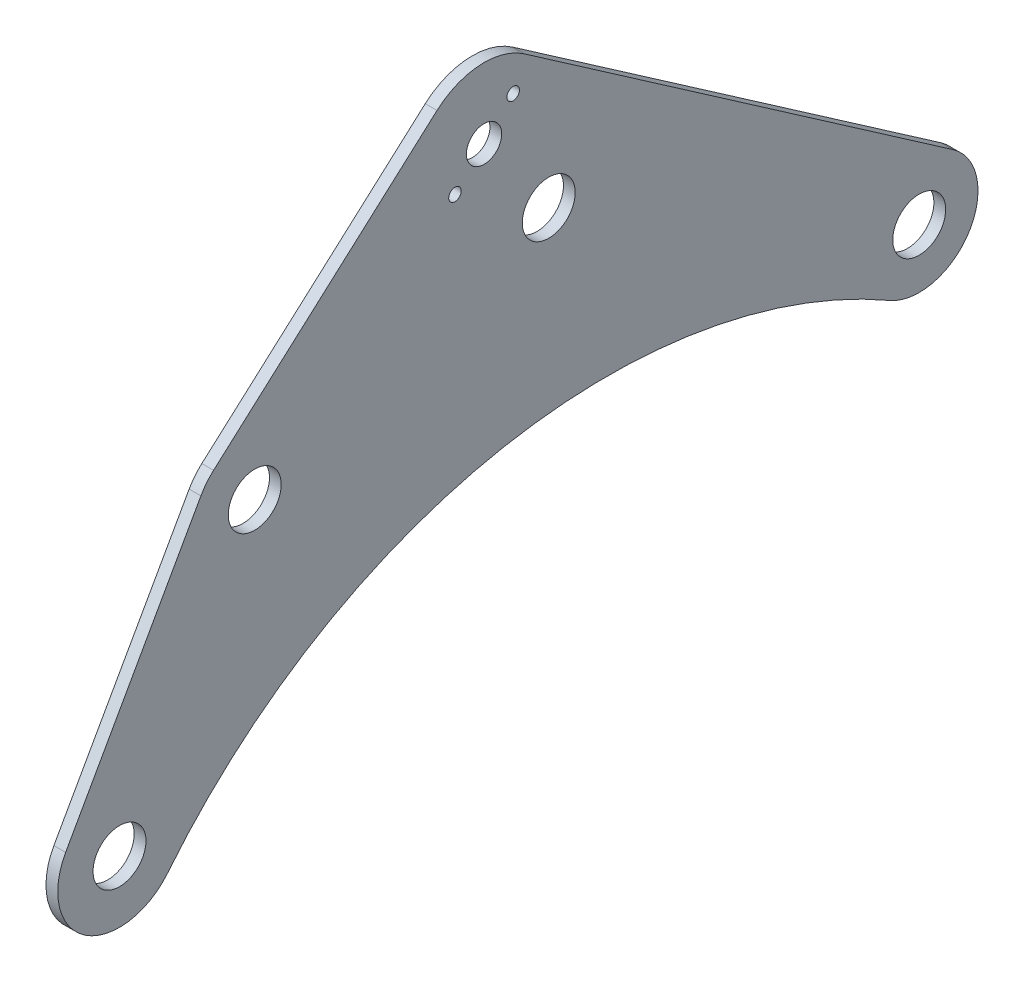
SolidWorks part; units mm, degrees
material "Acrylic (Medium-high impact)"
ref_plane "Front Plane" through (0, 0, 0) normal (0, 0, 1) x (1, 0, 0)
ref_plane "Top Plane" through (0, 0, 0) normal (0, 1, 0) x (1, 0, 0)
ref_plane "Right Plane" through (0, 0, 0) normal (1, 0, 0) x (0, 0, -1)
sketch "Sketch1" plane through (0, 0, 0) normal (1, 0, 0) x (0, 0, -1)
  line L0 (-548.7618, -304.8) -> (152.435, -304.8)
  line L1 (-192.8252, -120.65) -> (-152.4, -120.65)
  line L2 (-234.95, -162.7748) -> (-234.95, -205.5252)
  line L3 (-192.8252, -247.65) -> (-152.4, -247.65)
  line L4 (-152.4, -120.65) -> (-152.4, -247.65)
  circle A1 centre (0, 0) radius 6.35
  circle A6 centre (-431.8, -79.375) radius 12.7
  circle A7 centre (-358.775, 50.8) radius 12.7
  circle A8 centre (-200.025, 107.95) radius 12.7
  arc A9 (-234.95, -205.5252) -> (-192.8252, -247.65) centre (-192.8252, -205.5252) ccw
  arc A10 (-192.8252, -120.65) -> (-234.95, -162.7748) centre (-192.8252, -162.7748) ccw
  circle A11 centre (-358.775, -182.354) radius 120.65
  circle A12 centre (-234.95, 155.194) radius 29.845
  dimension "D1" = 12.7
  dimension "D2" = 25.4
  dimension "D3" = 42.1248
  dimension "D4" = 127
  dimension "D7" = 184.15
  dimension "D6" = 241.3
  dimension "D16" = 59.69
  dimension "D5" = 82.55
  dimension "D8" = 304.8
  dimension "D9" = 152.4
  dimension "D10" = 431.8
  dimension "D11" = 79.375
  dimension "D12" = 358.775
  dimension "D13" = 50.8
  dimension "D14" = 200.025
  dimension "D15" = 107.95
  dimension "D17" = 234.95
  dimension "D18" = 155.194
sketch "Sketch2" plane through (0, 0, 0) normal (1, 0, 0) x (0, 0, -1)
  line L1 (-460.8751, -63.0646) -> (-387.8501, 67.1104)
  line L3 (-381.0036, 75.6451) -> (-260.3541, 183.5884)
  line L5 (-213.2394, 186.5031) -> (18.0922, 26.0909)
  arc A0 (-381.0036, 75.6451) -> (-387.8501, 67.1104) centre (-358.775, 50.8) ccw
  arc A2 (-460.8751, -63.0646) -> (-405.83, -100.2783) centre (-431.8, -79.375) ccw
  arc A4 (-213.2394, 186.5031) -> (-260.3541, 183.5884) centre (-234.95, 155.194) ccw
  arc A5 (-15.8859, -27.49) -> (18.0922, 26.0909) centre (0, 0) ccw
  arc A8 (-405.83, -100.2783) -> (-15.8859, -27.49) centre (-168.3901, -291.3944) cw
  circle A12 centre (-431.8, -79.375) radius 12.7 construction
  circle A13 centre (-358.775, 50.8) radius 12.7 construction
  dimension "D1" = 33.3375
  dimension "D2" = 63.5
  dimension "D3" = 76.2
  dimension "D4" = 304.8
extrude "Boss-Extrude1" add sketch "Sketch2" along normal blind 6.35
sketch "Sketch3" plane through (6.35, 0, 0) normal (1, 0, 0) x (0, 0, -1)
  line L0 (-219.2346, 170.9094) -> (-250.6654, 139.4786) construction
  line L1 (-234.95, 155.194) -> (-234.95, 205.0182) construction
  circle A0 centre (-200.025, 107.95) radius 14.2875
  circle A1 centre (-358.775, 50.8) radius 14.2875
  circle A2 centre (-431.8, -79.375) radius 14.2875
  circle A3 centre (-234.95, 155.194) radius 9.525
  circle A4 centre (0, 0) radius 14.2875
  circle A5 centre (-250.6654, 139.4786) radius 3.3782
  circle A8 centre (-219.2346, 170.9094) radius 3.3782
  point P18 (-234.95, 155.194)
  dimension "D1" = 19.05
  dimension "D2" = 28.575
  dimension "D3" = 6.7564
  dimension "D4" = 44.45
  dimension "D5" = 45
extrude "Cut-Extrude1" cut sketch "Sketch3" against normal up to next
